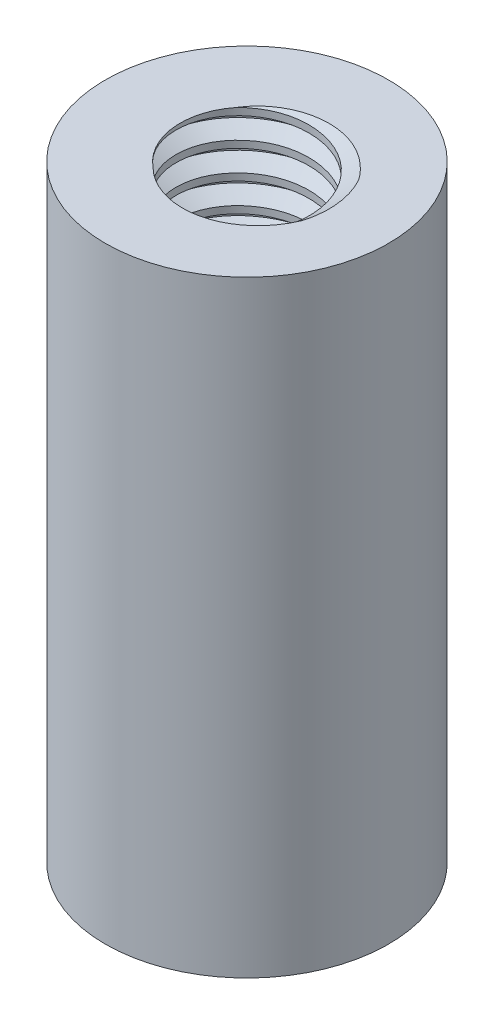
SolidWorks part; units mm, degrees
ref_plane "Front Plane" through (0, 0, 0) normal (0, 0, 1) x (1, 0, 0)
ref_plane "Top Plane" through (0, 0, 0) normal (0, 1, 0) x (1, 0, 0)
ref_plane "Right Plane" through (0, 0, 0) normal (1, 0, 0) x (0, 0, -1)
sketch "Sketch1" plane through (0, 0, 0) normal (0, 1, 0) x (1, 0, 0)
  circle A0 centre (0, 0) radius 3.5
  dimension "D1" = 7
extrude "Boss-Extrude1" add sketch "Sketch1" along normal mid plane 15
sketch "Sketch2" plane through (0, 7.5, 0) normal (0, 1, 0) x (1, 0, 0)
  circle A0 centre (0, 0) radius 1.65
  dimension "D1" = 3.3
extrude "Cut-Extrude1" cut sketch "Sketch2" against normal blind 6.5
thread "Thread1" pitch 0.7 method cut profile "Thread Profile1" start angle 0, offset 2, length 8, pitch 0.7, diameter 3.3
ref_plane "Plane1" through (-1.65, 9.5, 0) normal (0, 0, 1) x (-1, 0, 0)
sketch "Thread Profile1" plane through (-1.65, 9.5, 0) normal (0, 0, 1) x (-1, 0, 0)
  line L0 (0, 0) -> (0, 0.7) construction
  line L1 (0, 0) -> (0.3789, 0.2187)
  line L2 (0.3789, 0.2187) -> (0.3789, 0.3062)
  line L3 (0.3789, 0.3062) -> (0, 0.525)
  line L4 (0.3789, 0.2625) -> (0, 0.2625) construction
  line L11 (0, 0) -> (0, 0.525)
  point P2 (0, 0)
  dimension "Pitch" = 0.7
  dimension "Profile_Angle" = 60
  dimension "Profile_Land" = 0.0875
  dimension "Profile_Height" = 0.3789
mirror "Mirror3" about plane through (0, 0, 0) normal (0, 1, 0) of "Cut-Extrude1"
thread "Thread2" pitch 0.7 method cut profile "Thread Profile2" start angle 0, offset 2, length 8, pitch 0.7, diameter 3.3
ref_plane "Plane2" through (1.65, -9.5, 0) normal (0, 0, 1) x (1, 0, 0)
sketch "Thread Profile2" plane through (1.65, -9.5, 0) normal (0, 0, 1) x (1, 0, 0)
  line L0 (0, 0) -> (0, 0.7) construction
  line L1 (0, 0) -> (0.3789, 0.2187)
  line L2 (0.3789, 0.2187) -> (0.3789, 0.3062)
  line L3 (0.3789, 0.3062) -> (0, 0.525)
  line L4 (0.3789, 0.2625) -> (0, 0.2625) construction
  line L11 (0, 0) -> (0, 0.525)
  point P2 (0, 0)
  dimension "Pitch" = 0.7
  dimension "Profile_Angle" = 60
  dimension "Profile_Land" = 0.0875
  dimension "Profile_Height" = 0.3789
